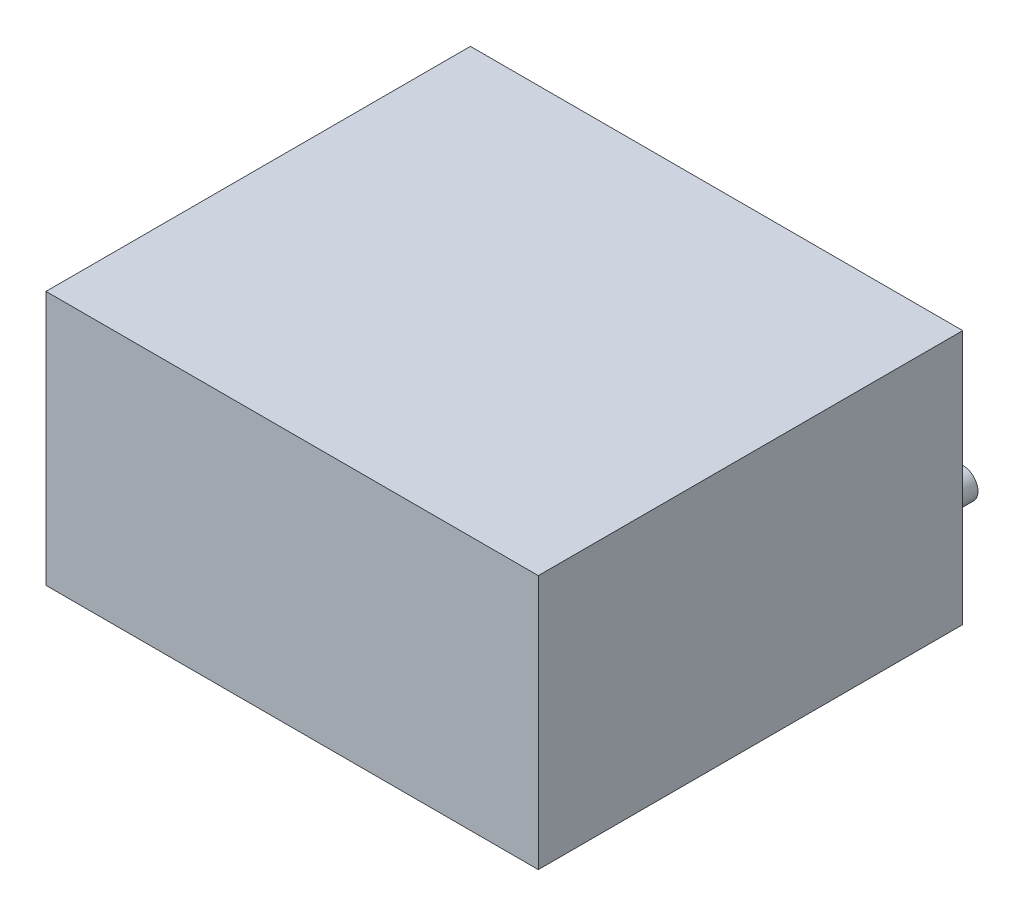
SolidWorks part; units mm, degrees
ref_plane "前视基准面" through (0, 0, 0) normal (0, 0, 1) x (1, 0, 0)
ref_plane "上视基准面" through (0, 0, 0) normal (0, 1, 0) x (1, 0, 0)
ref_plane "右视基准面" through (0, 0, 0) normal (1, 0, 0) x (0, 0, -1)
sketch "草图1" plane through (0, 0, 0) normal (0, 0, 1) x (1, 0, 0)
  line L0 (0, 0) -> (11.6, 0)
  line L1 (11.6, 0) -> (11.6, 6)
  line L2 (11.6, 6) -> (0, 6)
  line L3 (0, 6) -> (0, 0)
  dimension "D1" = 11.6
  dimension "D2" = 6
extrude "凸台-拉伸1" add sketch "草图1" along normal blind 10
sketch "草图2" plane through (0, 0, 0) normal (0, 0, -1) x (-1, 0, 0)
  line L0 (0, 0.9) -> (-11.6, 0.9) construction
  line L1 (0, 6) -> (0, 0) construction
  line L2 (-11.6, 0) -> (-11.6, 6) construction
  line L3 (0, 0) -> (-11.6, 0) construction
  line L4 (-5.8, 0) -> (-5.8, 6) construction
  line L5 (-11.6, 6) -> (0, 6) construction
  circle A0 centre (-7.07, 0.9) radius 0.35
  circle A1 centre (-9.61, 0.9) radius 0.35
  circle A2 centre (-1.99, 0.9) radius 0.35
  circle A3 centre (-4.53, 0.9) radius 0.35
  dimension "D2" = 0.7
  dimension "D3" = 2.54
  dimension "D4" = 0.7
  dimension "D5" = 7.62
  dimension "D1" = 0.9
extrude "凸台-拉伸2" add sketch "草图2" along normal blind 2
sketch "草图3" plane through (0, 0, 0) normal (0, -1, 0) x (1, 0, 0)
  line L0 (0, 6.8592) -> (11.6, 6.8592) construction
  line L1 (0, 10) -> (0, 0) construction
  line L2 (11.6, 10) -> (11.6, 0) construction
  line L3 (0, 3.2238) -> (11.6, 3.2238) construction
  text T0 "MORNSUN" height in points 5
  text T1 "B0505S-1W" height in points 5
wrap "包覆1" sketch "草图3" wrap type scribe source sketch "草图3" face at (5.8, 0, 5)
